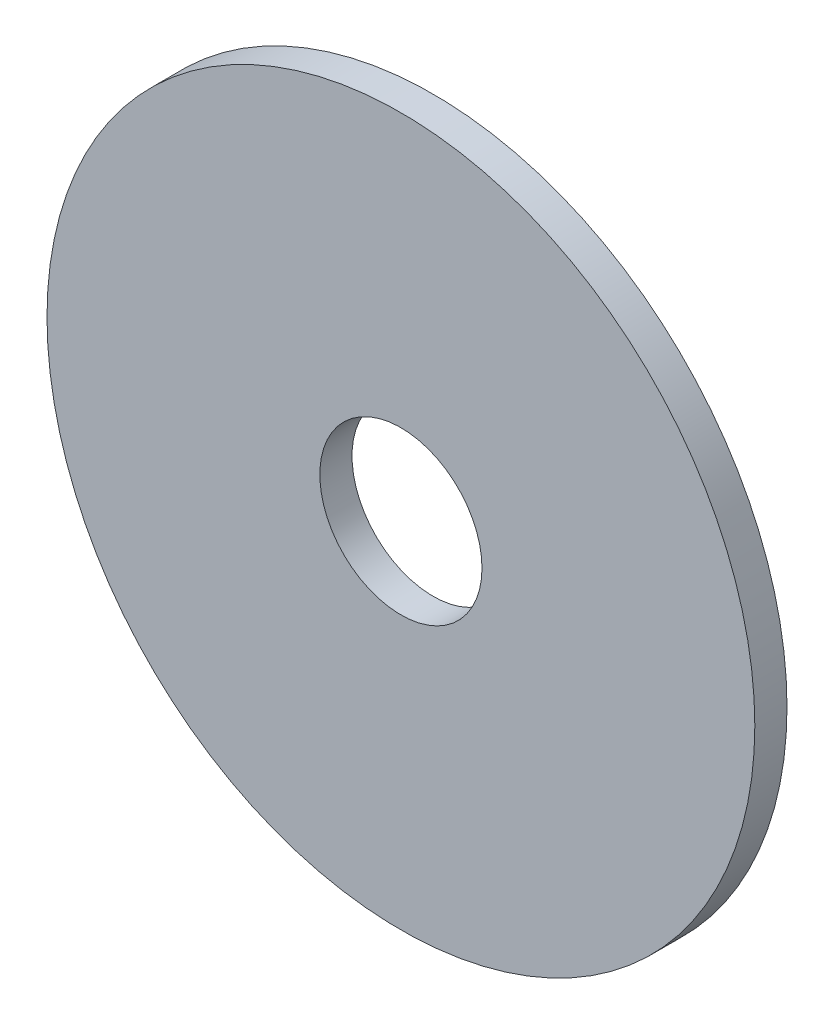
SolidWorks part; units mm, degrees
ref_plane "Front Plane" through (0, 0, 0) normal (0, 0, 1) x (1, 0, 0)
ref_plane "Top Plane" through (0, 0, 0) normal (0, 1, 0) x (1, 0, 0)
ref_plane "Right Plane" through (0, 0, 0) normal (1, 0, 0) x (0, 0, -1)
sketch "Sketch1" plane through (0, 0, 0) normal (0, 0, 1) x (1, 0, 0)
  circle A0 centre (0, 0) radius 34.925
  circle A1 centre (0, 0) radius 8.001
  dimension "D1" = 69.85
  dimension "D2" = 16.002
extrude "Boss-Extrude1" add sketch "Sketch1" along normal blind 3.175 contours A1 | A0 region at (0, 0, 0)
